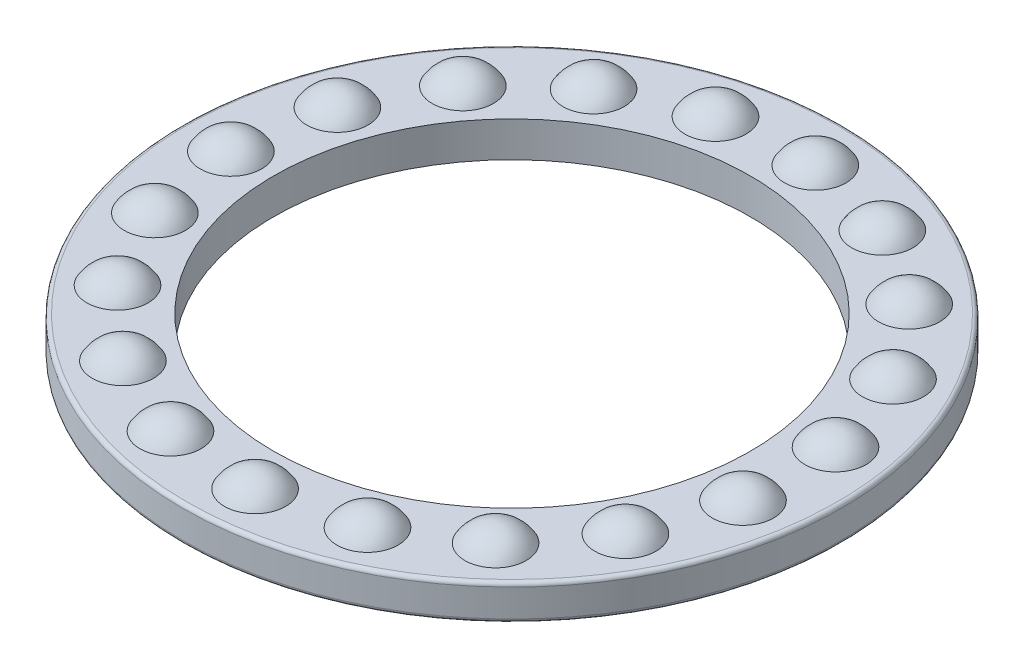
SolidWorks part; units mm, degrees
ref_plane "Front Plane" through (0, 0, 0) normal (0, 0, 1) x (1, 0, 0)
ref_plane "Top Plane" through (0, 0, 0) normal (0, 1, 0) x (1, 0, 0)
ref_plane "Right Plane" through (0, 0, 0) normal (1, 0, 0) x (0, 0, -1)
sketch "Sketch1" plane through (0, 0, 0) normal (0, 1, 0) x (1, 0, 0)
  circle A0 centre (0, 0) radius 85
  circle A1 centre (0, 0) radius 61.5
  dimension "D1" = 170
  dimension "D2" = 123
extrude "Boss-Extrude1" add sketch "Sketch1" along normal blind 9.13
ref_axis "Axis1" through (0, 9.13, 0) along (0, -1, 0)
fillet "Fillet2" radius 1 2 edges at (0, 0, 85) (0, 9.13, 85)
sketch "Sketch3" plane through (0, 0, 0) normal (0, 0, 1) x (1, 0, 0)
  line L0 (-85, 4.565) -> (-46.4642, 4.565) construction
  line L1 (-85, 8.13) -> (-85, 1) construction
  line L2 (-72.5, -4.565) -> (-72.5, 13.695)
  arc A0 (-72.5, -4.565) -> (-72.5, 13.695) centre (-72.5, 4.565) ccw
  dimension "D1" = 18.26
  dimension "D2" = 72.5
revolve "Revolve1" add sketch "Sketch3" angle 360 about L2
pattern_circular "CirPattern1" count 19 every 18.947 about axis through (0, 9.13, 0) along (0, -1, 0) of "Revolve1"
